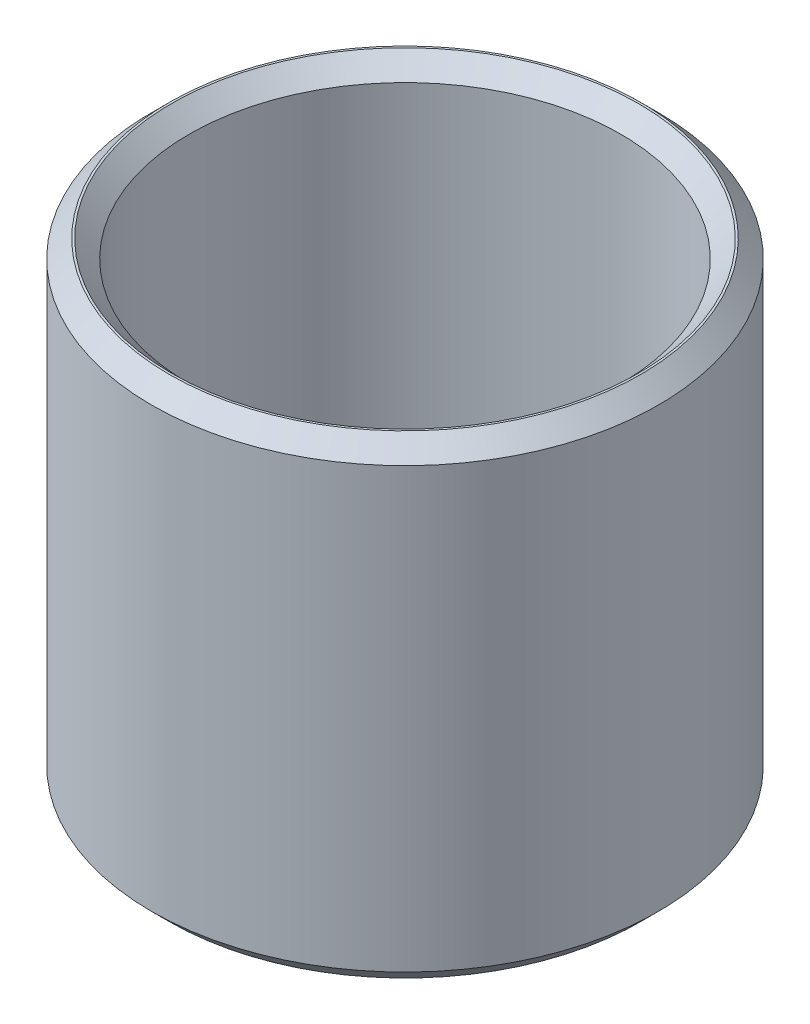
SolidWorks part; units mm, degrees
ref_plane "Front Plane" through (0, 0, 0) normal (0, 0, 1) x (1, 0, 0)
ref_plane "Top Plane" through (0, 0, 0) normal (0, 1, 0) x (1, 0, 0)
ref_plane "Right Plane" through (0, 0, 0) normal (1, 0, 0) x (0, 0, -1)
sketch "Sketch1" plane through (0, 0, 0) normal (0, 1, 0) x (1, 0, 0)
  circle A0 centre (0, 0) radius 32.5
  dimension "SLEEVE_OD" = 65
extrude "Boss-Extrude1" add sketch "Sketch1" along normal blind 60.7918
sketch "Sketch2" plane through (0, 0, 0) normal (0, 1, 0) x (1, 0, 0)
  circle A0 centre (0, 0) radius 27.6942
  dimension "BORE_D" = 55.3884
extrude "Cut-Extrude1" cut sketch "Sketch2" along normal through all
chamfer "Chamfer1" distance 2.2671 angle 45 4 edges at (0, 60.7918, 27.6942) (0, 0, 27.6942) (0, 0, 32.5) (0, 60.7918, 32.5)
